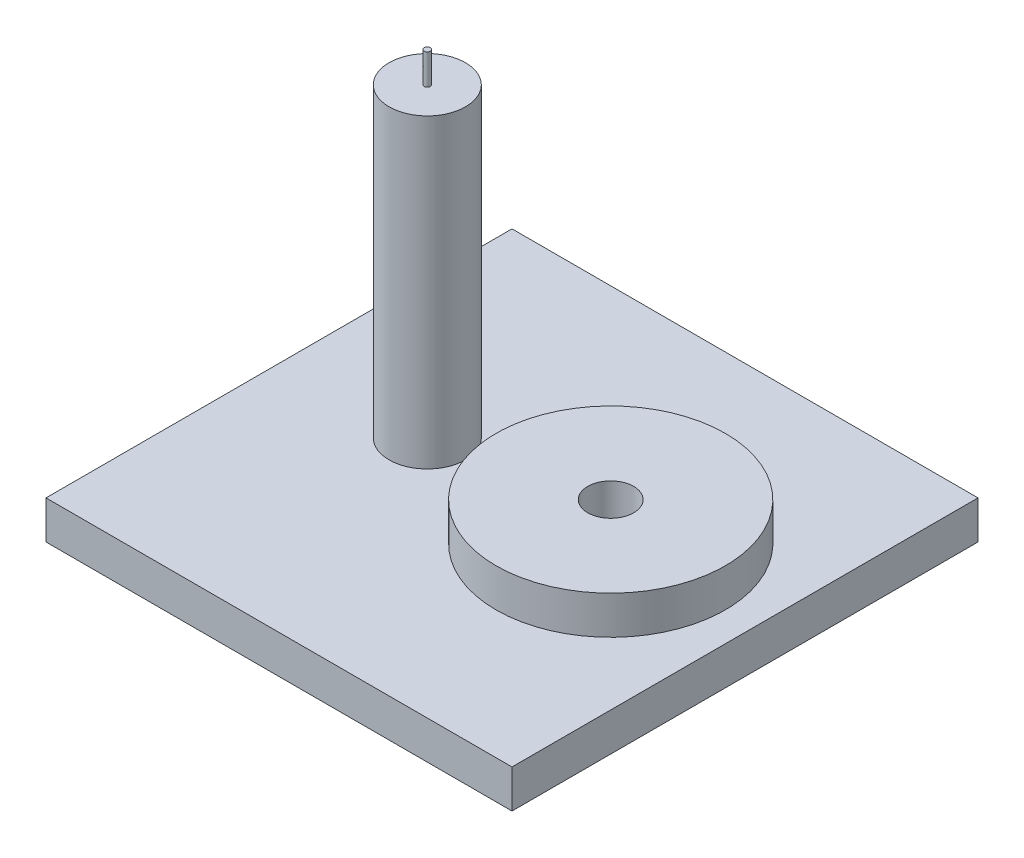
SolidWorks part; units mm, degrees
ref_plane "Front Plane" through (0, 0, 0) normal (0, 0, 1) x (1, 0, 0)
ref_plane "Top Plane" through (0, 0, 0) normal (0, 1, 0) x (1, 0, 0)
ref_plane "Right Plane" through (0, 0, 0) normal (1, 0, 0) x (0, 0, -1)
sketch "Sketch1" plane through (0, 0, 0) normal (0, 1, 0) x (1, 0, 0)
  line L1 (-143.2501, 146.0814) -> (161.5499, 146.0814)
  line L2 (-143.2501, 146.0814) -> (-143.2501, -158.7186)
  line L3 (-143.2501, -158.7186) -> (161.5499, -158.7186)
  line L4 (161.5499, 146.0814) -> (161.5499, -158.7186)
  dimension "D1" = 304.8
  dimension "D2" = 304.8
extrude "Boss-Extrude1" add sketch "Sketch1" along normal blind 25
sketch "Sketch2" plane through (0, 25, 0) normal (0, 1, 0) x (1, 0, 0)
  circle A0 centre (67.3894, 0) radius 75
extrude "Boss-Extrude2" add sketch "Sketch2" along normal blind 25
sketch "Sketch3" plane through (0, 50, 0) normal (0, 1, 0) x (1, 0, 0)
  circle A0 centre (67.3894, 0) radius 15
extrude "Cut-Extrude1" cut sketch "Sketch3" against normal blind 25
sketch "Sketch4" plane through (0, 25, 0) normal (0, 1, 0) x (1, 0, 0)
  circle A0 centre (-52.5758, 0) radius 25
extrude "Boss-Extrude3" add sketch "Sketch4" along normal blind 200
sketch "Sketch5" plane through (0, 225, 0) normal (0, 1, 0) x (1, 0, 0)
  circle A0 centre (-52.5758, 0) radius 2
extrude "Boss-Extrude4" add sketch "Sketch5" along normal blind 20
